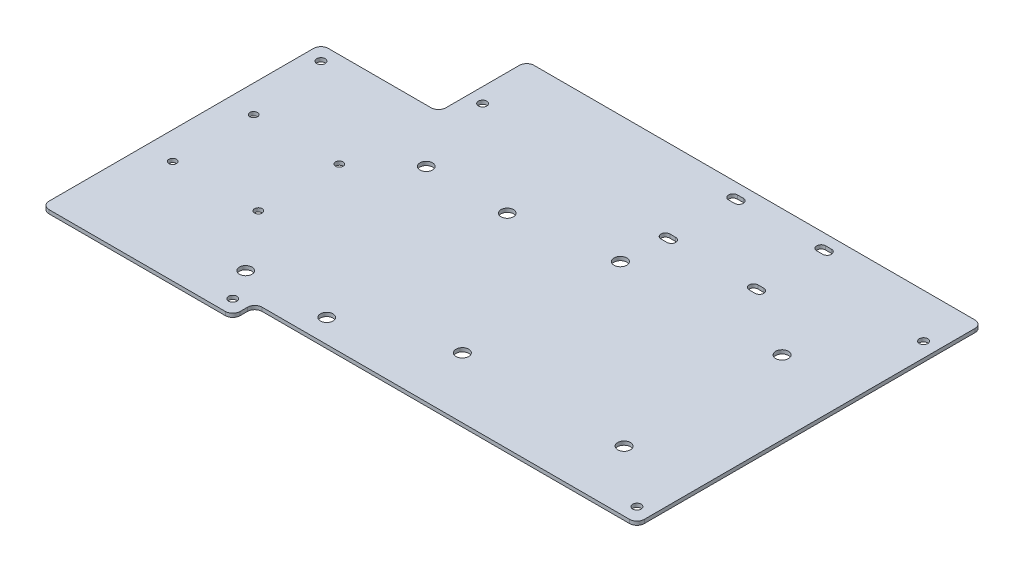
SolidWorks part; units mm, degrees
ref_plane "Front Plane" through (0, 0, 0) normal (0, 0, 1) x (1, 0, 0)
ref_plane "Top Plane" through (0, 0, 0) normal (0, 1, 0) x (1, 0, 0)
ref_plane "Right Plane" through (0, 0, 0) normal (1, 0, 0) x (0, 0, -1)
sketch "Sketch1" plane through (0, 0, 0) normal (0, 1, 0) x (1, 0, 0)
  line L1 (0, 0) -> (247.65, 0)
  line L2 (0, 0) -> (0, 120.65)
  line L3 (50.8, 158.75) -> (247.65, 158.75)
  line L4 (247.65, 0) -> (247.65, 158.75)
  line L15 (0, 120.65) -> (50.8, 120.65)
  line L16 (50.8, 158.75) -> (50.8, 120.65)
  line L21 (351.9786, 184.7613) -> (351.9786, -3.4747) construction
  dimension "D1" = 158.75
  dimension "D2" = 351.9786
  dimension "D4" = 247.65
  dimension "D6" = 38.1
  dimension "D7" = 50.8
extrude "Boss-Extrude1" add sketch "Sketch1" along normal blind 1.6002 contours L1 L4 L3 L2 L15 L16 region at (128.9214, 0, -76.2514)
sketch "Sketch3" plane through (0, 1.6002, 0) normal (0, 1, 0) x (1, 0, 0)
  line L0 (82.55, 0) -> (82.55, 9.525)
  line L1 (0, 0) -> (247.65, 0) construction
  line L2 (82.55, 9.525) -> (247.65, 9.525)
  line L8 (247.65, 0) -> (247.65, 158.75) construction
  line L10 (247.65, 0) -> (82.55, 0)
  line L11 (0, 0) -> (0, 120.65) construction
  line L12 (247.65, 9.525) -> (247.65, 0)
  dimension "D1" = 82.55
  dimension "D2" = 9.525
extrude "Cut-Extrude1" cut sketch "Sketch3" against normal through all
fillet "Fillet1" radius 3.175 8 edges at (82.55, 0.8001, 0) (0, 0.8001, -120.65) (50.8, 0.8001, -120.65) (50.8, 0.8001, -158.75) (247.65, 0.8001, -158.75) (247.65, 0.8001, -9.525) (82.55, 0.8001, -9.525) (0, 0.8001, 0)
sketch "Sketch4" plane through (0, 1.6002, 0) normal (0, 1, 0) x (1, 0, 0)
  line L0 (146.365, 152.32) -> (148.905, 152.32) construction
  line L1 (146.365, 154.225) -> (148.905, 154.225)
  line L2 (146.365, 150.415) -> (148.905, 150.415)
  line L5 (184.465, 152.32) -> (187.005, 152.32) construction
  line L6 (184.465, 154.225) -> (187.005, 154.225)
  line L7 (184.465, 150.415) -> (187.005, 150.415)
  line L8 (184.465, 123.11) -> (187.005, 123.11) construction
  line L9 (184.465, 125.015) -> (187.005, 125.015)
  line L10 (184.465, 121.205) -> (187.005, 121.205)
  line L11 (146.365, 123.11) -> (148.905, 123.11) construction
  line L12 (146.365, 125.015) -> (148.905, 125.015)
  line L13 (146.365, 121.205) -> (148.905, 121.205)
  line L15 (185.735, 123.11) -> (147.635, 123.11) construction
  line L16 (185.735, 123.11) -> (185.735, 152.32) construction
  line L17 (185.735, 152.32) -> (147.635, 152.32) construction
  line L18 (147.635, 123.11) -> (147.635, 152.32) construction
  line L19 (185.735, 123.11) -> (147.635, 152.32) construction
  line L20 (185.735, 152.32) -> (147.635, 123.11) construction
  line L21 (203.2, 125.015) -> (130.17, 125.015) construction
  line L22 (203.2, 125.015) -> (203.2, 150.415) construction
  line L23 (203.2, 150.415) -> (130.17, 150.415) construction
  line L24 (130.17, 125.015) -> (130.17, 150.415) construction
  line L25 (203.2, 125.015) -> (130.17, 150.415) construction
  line L26 (203.2, 150.415) -> (130.17, 125.015) construction
  arc A0 (146.365, 154.225) -> (146.365, 150.415) centre (146.365, 152.32) ccw
  arc A1 (148.905, 150.415) -> (148.905, 154.225) centre (148.905, 152.32) ccw
  arc A2 (184.465, 154.225) -> (184.465, 150.415) centre (184.465, 152.32) ccw
  arc A3 (187.005, 150.415) -> (187.005, 154.225) centre (187.005, 152.32) ccw
  arc A4 (184.465, 125.015) -> (184.465, 121.205) centre (184.465, 123.11) ccw
  arc A5 (187.005, 121.205) -> (187.005, 125.015) centre (187.005, 123.11) ccw
  arc A6 (146.365, 125.015) -> (146.365, 121.205) centre (146.365, 123.11) ccw
  arc A7 (148.905, 121.205) -> (148.905, 125.015) centre (148.905, 123.11) ccw
  point P2 (147.635, 152.32)
  point P12 (166.685, 137.715)
  point P13 (185.735, 152.32)
  point P20 (185.735, 123.11)
  point P27 (147.635, 123.11)
  point P36 (166.685, 137.715)
  dimension "D2" = 6.35
  dimension "D1" = 3.81
  dimension "D5" = 38.1
  dimension "D3" = 2
  dimension "D4" = 2
extrude "Fuse Ziptie Mounts" cut sketch "Sketch4" against normal through all
sketch "Sketch5" plane through (0, 1.6002, 0) normal (0, 1, 0) x (1, 0, 0)
  circle A0 centre (146.05, 103.9876) radius 2.75
  circle A1 centre (146.05, 35.7124) radius 2.75
  circle A2 centre (215.9, 103.9876) radius 2.75
  circle A3 centre (215.9, 35.7124) radius 2.75
  dimension "D1" = 5.5
extrude "Contactor Mounting Holes" cut sketch "Sketch5" against normal through all
sketch "Sketch6" plane through (0, 1.6002, 0) normal (0, 1, 0) x (1, 0, 0)
  line L0 (0, 3.175) -> (0, 117.475) construction
  line L1 (3.175, 120.65) -> (47.625, 120.65) construction
  line L2 (82.55, 6.35) -> (82.55, 3.175) construction
  line L3 (3.175, 0) -> (79.375, 0) construction
  line L4 (244.475, 9.525) -> (85.725, 9.525) construction
  line L5 (247.65, 12.7) -> (247.65, 155.575) construction
  line L6 (53.975, 158.75) -> (244.475, 158.75) construction
  line L7 (50.8, 155.575) -> (50.8, 123.825) construction
  circle A0 centre (6.35, 114.3) radius 1.8288
  circle A1 centre (76.2, 6.35) radius 1.8288
  circle A2 centre (241.3, 15.875) radius 1.8288
  circle A3 centre (241.3, 139.7) radius 1.8288
  circle A4 centre (57.15, 133.35) radius 1.8288
  dimension "D1" = 3.6576
  dimension "D2" = 6.35
  dimension "D3" = 6.35
  dimension "D4" = 6.35
  dimension "D5" = 6.35
  dimension "D6" = 6.35
  dimension "D7" = 6.35
  dimension "D8" = 19.05
  dimension "D9" = 6.35
  dimension "D10" = 25.4
extrude "Cut-Extrude2" cut sketch "Sketch6" against normal through all
sketch "Sketch7" plane through (0, 1.6002, 0) normal (0, 1, 0) x (1, 0, 0)
  line L0 (68.5, 97.65) -> (68.5, 19.65) construction
  line L1 (103.5, 19.65) -> (103.5, 97.65) construction
  circle A0 centre (103.5, 19.65) radius 2.7051
  circle A1 centre (68.5, 19.65) radius 2.7051
  circle A2 centre (103.5, 97.65) radius 2.7051
  circle A3 centre (68.5, 97.65) radius 2.7051
  point P2 (103.5, 19.65)
  point P5 (103.5, 97.65)
  dimension "D1" = 5.4102
  dimension "D2" = 35
extrude "Cut-Extrude3" cut sketch "Sketch7" against normal through all
sketch "Sketch9" plane through (0, 1.6002, 0) normal (0, 1, 0) x (1, 0, 0)
  circle A0 centre (11.85, 79.75) radius 1.65
  circle A1 centre (11.85, 44.75) radius 1.65
  circle A2 centre (48.85, 79.75) radius 1.65
  circle A3 centre (48.85, 44.75) radius 1.65
  dimension "D1" = 3.3
extrude "Cut-Extrude4" cut sketch "Sketch9" against normal through all
